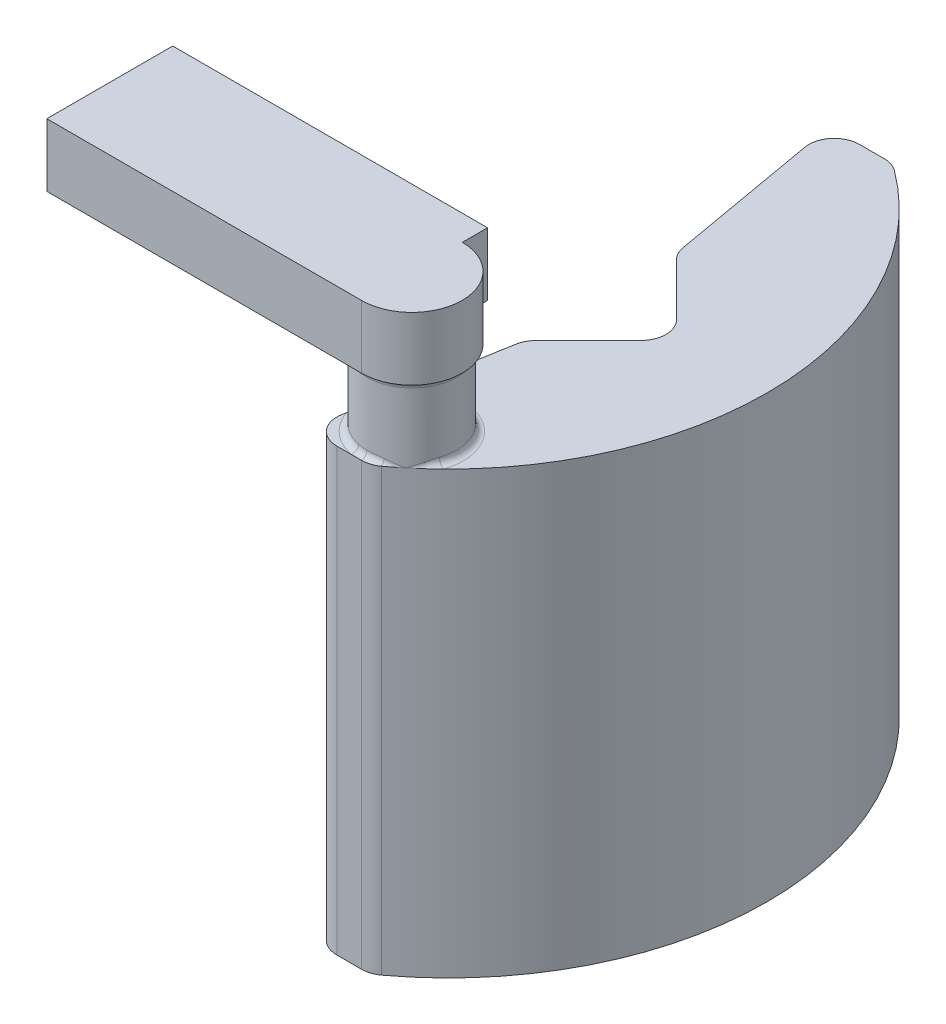
SolidWorks part; units mm, degrees
material "ABS PC"
ref_plane "Alzado" through (0, 0, 0) normal (0, 0, 1) x (1, 0, 0)
ref_plane "Planta" through (0, 0, 0) normal (0, 1, 0) x (1, 0, 0)
ref_plane "Vista lateral" through (0, 0, 0) normal (1, 0, 0) x (0, 0, -1)
sketch "Croquis1" plane through (0, 0, 0) normal (0, 1, 0) x (1, 0, 0)
  line L0 (4.5996, 6.007) -> (10.6066, 0)
  line L1 (-18.5, -18.5) -> (18.5, -18.5) construction
  line L2 (-18.5, -18.5) -> (-18.5, 18.5) construction
  line L3 (-18.5, 18.5) -> (18.5, 18.5) construction
  line L4 (18.5, -18.5) -> (18.5, 18.5) construction
  line L5 (-18.5, -18.5) -> (18.5, 18.5) construction
  line L6 (-18.5, 18.5) -> (18.5, -18.5) construction
  line L7 (-20.75, -20.75) -> (20.75, -20.75) construction
  line L8 (-20.75, -20.75) -> (-20.75, 20.75) construction
  line L9 (-20.75, 20.75) -> (20.75, 20.75) construction
  line L10 (20.75, -20.75) -> (20.75, 20.75) construction
  line L11 (-20.75, -20.75) -> (20.75, 20.75) construction
  line L12 (-20.75, 20.75) -> (20.75, -20.75) construction
  line L13 (10.6066, 0) -> (4.5996, -6.007)
  line L14 (4.5996, 6.007) -> (4.5996, -6.007) construction
  line L15 (-20.75, 0) -> (20.75, 0) construction
  line L16 (0, 20.75) -> (0, -20.75) construction
  line L17 (2, 20.75) -> (4.5996, 6.007)
  line L18 (4.5996, -6.007) -> (2, -20.75)
  line L19 (2, 20.75) -> (2, -20.75) construction
  line L20 (2, 20.75) -> (7, 20.75)
  line L21 (2, -20.75) -> (7, -20.75)
  circle A0 centre (0, 0) radius 7.5 construction
  arc A1 (7, 20.75) -> (7, -20.75) centre (-7.5, 0) cw
  point P0 (0, 0)
  point P5 (0, 0)
  point P18 (4.5996, 0)
  dimension "D5" = 15
  dimension "D1" = 37
  dimension "D2" = 37
  dimension "D3" = 2.25
  dimension "D4" = 2.25
  dimension "D6" = 10
  dimension "D7" = 2
  dimension "D8" = 5
  dimension "D9" = 5
extrude "Saliente-Extruir1" add sketch "Croquis1" along normal blind 35
fillet "Redondeo1" radius 2 7 edges at (4.5996, 17.5, -6.007) (4.5996, 17.5, 6.007) (7, 17.5, -20.75) (7, 17.5, 20.75) (2, 17.5, 20.75) (2, 17.5, -20.75) (10.6066, 17.5, 0)
sketch "Croquis3" plane through (0, 35, 0) normal (0, 1, 0) x (1, 0, 0)
  line L0 (2.4139, 18.4027) -> (2.4139, -18.4027) construction
  line L2 (6.3562, -20.75) -> (-18.6438, -20.75)
  line L3 (6.3562, -20.75) -> (6.3562, -12.75)
  line L4 (6.3562, -12.75) -> (-18.6438, -12.75)
  line L5 (-18.6438, -20.75) -> (-18.6438, -12.75)
  line L6 (2.4139, 18.4027) -> (4.4901, 6.628)
  line L7 (5.0455, 5.5611) -> (9.1924, 1.4142)
  line L8 (9.1924, -1.4142) -> (5.0455, -5.5611)
  line L9 (4.4901, -6.628) -> (2.4139, -18.4027)
  line L10 (4.3835, -20.75) -> (6.3562, -20.75)
  line L11 (6.3562, 20.75) -> (4.3835, 20.75)
  line L12 (2.4139, 18.4027) -> (4.4901, 6.628)
  line L13 (5.0455, 5.5611) -> (9.1924, 1.4142)
  line L14 (9.1924, -1.4142) -> (5.0455, -5.5611)
  line L15 (4.4901, -6.628) -> (2.4139, -18.4027)
  line L16 (4.3835, -20.75) -> (6.3562, -20.75)
  line L17 (6.3562, 20.75) -> (4.3835, 20.75)
  line L20 (-18.6438, -12.75) -> (6.3562, -12.75) construction
  line L21 (-18.6438, -12.75) -> (-18.6438, -10.75)
  line L22 (-18.6438, -10.75) -> (6.3562, -10.75)
  line L23 (6.3562, -12.75) -> (6.3562, -10.75)
  circle A0 centre (6.3442, -16.75) radius 3.5836
  arc A1 (6.3562, -12.75) -> (6.3562, -20.75) centre (6.3442, -16.75) cw
  arc A8 (4.4901, 6.628) -> (5.0455, 5.5611) centre (6.4597, 6.9753) ccw
  arc A9 (9.1924, -1.4142) -> (9.1924, 1.4142) centre (7.7782, 0) ccw
  arc A10 (5.0455, -5.5611) -> (4.4901, -6.628) centre (6.4597, -6.9753) ccw
  arc A11 (2.4139, -18.4027) -> (4.3835, -20.75) centre (4.3835, -18.75) ccw
  arc A12 (6.3562, -20.75) -> (7.5448, -20.3585) centre (6.3562, -18.75) ccw
  arc A13 (7.5448, -20.3585) -> (7.5448, 20.3585) centre (-7.5, 0) ccw
  arc A14 (7.5448, 20.3585) -> (6.3562, 20.75) centre (6.3562, 18.75) ccw
  arc A15 (4.3835, 20.75) -> (2.4139, 18.4027) centre (4.3835, 18.75) ccw
  arc A16 (4.4901, 6.628) -> (5.0455, 5.5611) centre (6.4597, 6.9753) ccw
  arc A17 (9.1924, -1.4142) -> (9.1924, 1.4142) centre (7.7782, 0) ccw
  arc A18 (5.0455, -5.5611) -> (4.4901, -6.628) centre (6.4597, -6.9753) ccw
  arc A19 (2.4139, -18.4027) -> (4.3835, -20.75) centre (4.3835, -18.75) ccw
  arc A20 (6.3562, -20.75) -> (7.5448, -20.3585) centre (6.3562, -18.75) ccw
  arc A21 (7.5448, -20.3585) -> (7.5448, 20.3585) centre (-7.5, 0) ccw
  arc A22 (7.5448, 20.3585) -> (6.3562, 20.75) centre (6.3562, 18.75) ccw
  arc A23 (4.3835, 20.75) -> (2.4139, 18.4027) centre (4.3835, 18.75) ccw
  point P2 (17.8143, 0)
  line M31 (4.4901, -6.628) -> (2.4139, -18.4027)
  arc M32 (2.4139, -18.4027) -> (4.3835, -20.75) centre (4.3835, -18.75) ccw
  line M33 (4.3835, -20.75) -> (6.3562, -20.75)
  arc M34 (6.3562, -20.75) -> (7.5448, -20.3585) centre (6.3562, -18.75) ccw
  arc M35 (7.5448, -20.3585) -> (7.5448, 20.3585) centre (-7.5, 0) ccw
  dimension "D5" = 7.1671
  dimension "D6" = 2
  dimension "D2" = 8
  dimension "D3" = 11.4581
  dimension "D4" = 25
  dimension "D1" = 0
extrude "Saliente-Extruir2" add sketch "Croquis3" along normal blind 6 contours L3 A0 | L3 A0 region at (4.8297, 35, 16.75) region at (7.8716, 35, 16.75)
extrude "Saliente-Extruir4" add sketch "Croquis3<4>" along normal blind 5 from surface contours L5 L2 L15 L4 M32 M31 | A0 L15 L3 M32 M33 | A0 L3 L4 M31 | L3 A0 | L3 A0 | A1 L3 A0 M35 | A1 M35 M34 | A1 A0 L3 M34 M35 | L22 L21 L4 L15 | L4 L23 L22 L15 region at (3.7634, 35, 19.5923) region at (8.6815, 35, 19.6558) region at (7.0606, 35, 20.3921) region at (-7.8867, 35, 16.732) region at (4.8297, 35, 16.75) region at (7.8716, 35, 16.75) region at (9.3026, 35, 18.8287) region at (4.2802, 35, 13.4651) region at (4.9697, 35, 11.7712) region at (-7.5282, 35, 11.7474) starting at face at (6.3442, 41, 20.3336)
sketch "Croquis3<4>" plane through (0, 35, 0) normal (0, 1, 0) x (1, 0, 0) same geometry as "Croquis3"
fillet "Redondeo2" radius 0.5 3 edges at (6.3442, 41, 20.3336) (8.1475, 35, 13.6532) (4.5409, 35, 19.8468)
equation "\"D9@Croquis1\"=\"D8@Croquis1\""
